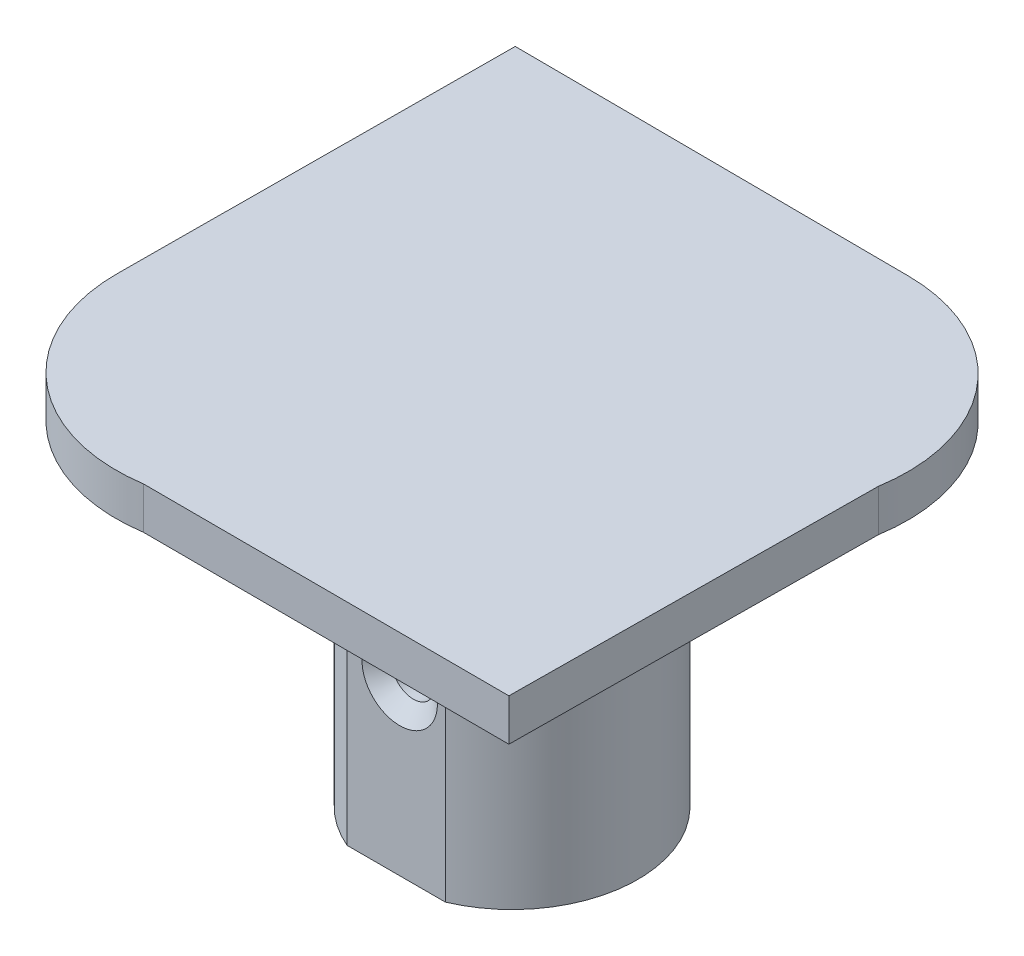
SolidWorks part; units mm, degrees
other "Camera1"
material "ABS"
ref_plane "Front Plane" through (0, 0, 0) normal (0, 0, 1) x (1, 0, 0)
ref_plane "Top Plane" through (0, 0, 0) normal (0, 1, 0) x (1, 0, 0)
ref_plane "Right Plane" through (0, 0, 0) normal (1, 0, 0) x (0, 0, -1)
sketch "Sketch2" plane through (0, 0, 0) normal (0, 1, 0) x (1, 0, 0)
  line L0 (2.8358, -0.2904) -> (10.2697, -0.2904)
  line L1 (2.8358, 17.2492) -> (10.2697, 17.2492)
  line L2 (6.5528, -0.2904) -> (6.5528, 17.2492) construction
  arc A0 (2.8358, 17.2492) -> (2.8358, -0.2904) centre (6.5528, 8.4794) ccw
  circle A1 centre (6.5528, 8.4794) radius 6.35
  arc A2 (10.2697, -0.2904) -> (10.2697, 17.2492) centre (6.5528, 8.4794) ccw
  dimension "D1" = 12.7
  dimension "D2" = 3.175
sketch "Sketch3" plane through (0, 0, 0) normal (0, 1, 0) x (1, 0, 0)
  line L0 (0, -12.8694) -> (27.7233, -12.933)
  line L1 (-14.7878, -0.0506) -> (-14.6178, 29.8917)
  line L4 (-14.6178, 29.8917) -> (27.7233, -12.933) construction
  line L5 (27.9746, 14.7893) -> (27.7233, -12.933)
  line L6 (15.3245, 29.7217) -> (-14.6178, 29.8917)
  arc A0 (-14.7878, -0.0506) -> (0, -12.8694) centre (-1.9188, -0.1438) ccw
  arc A2 (15.3245, 29.7217) -> (27.9746, 14.7893) centre (15.2716, 16.8524) cw
  point P8 (6.5528, 8.4794)
  dimension "D1" = 12.8694
extrude "Boss-Extrude1" add sketch "Sketch3" along normal blind 3.175 contours L4 L1 A0 L0 | L6 L4 L5 A2 | L0 L5 A2 L6 L1 A0 region at (-0.1371, 0, -1.8095) region at (13.2982, 0, -15.093)
ref_plane "Plane6" through (0, 0, 0) normal (0, -1, 0) x (-1, 0, 0)
sketch "Sketch11" plane through (0, 0, 0) normal (0, 1, 0) x (1, 0, 0)
  line L0 (20.07, -8.458) -> (21.4908, -8.4607)
  spline S0 degree 3 poles (22.9265, -1.3184) (22.9265, -4.6505) (22.9265, -7.9835) (22.9265, -11.3169) knots 3 3 3 3 4 4 4 4
  spline S1 degree 3 poles (12.9265, -1.3184) (16.2589, -1.3184) (19.5927, -1.3184) (22.9265, -1.3184) knots 2 2 2 2 3 3 3 3
  spline S2 degree 3 poles (12.9265, -11.3169) (12.9265, -7.9851) (12.9265, -4.6531) (12.9265, -1.3184) knots 1 1 1 1 2 2 2 2
  spline S3 degree 3 poles (22.9265, -11.3169) (19.5937, -11.3169) (16.2609, -11.3169) (12.9265, -11.3169) knots 0 0 0 0 1 1 1 1
  spline S4 degree 3 poles (15.7816, -4.1748) (17.1943, -4.1744) (20.0443, -4.1757) (20.0617, -4.1773) knots 0 0 0 0 1 1 1 1
  spline S5 degree 3 poles (20.0617, -4.1773) (20.0642, -4.1931) (20.0678, -7.048) (20.0673, -8.4607) knots 1 1 1 1 2 2 2 2
  spline S6 degree 2 poles (20.0673, -8.4607) (18.1734, -8.458) (17.2149, -8.458) knots 2 2 2 3 3 3
  spline S7 degree 3 poles (17.2149, -8.458) (17.2149, -8.9351) (17.2149, -9.4058) (17.2149, -9.8824) knots 3 3 3 3 4 4 4 4
  spline S8 degree 3 poles (17.2149, -9.8824) (16.7341, -9.8824) (16.2635, -9.8824) (15.7859, -9.8824) knots 4 4 4 4 5 5 5 5
  spline S9 degree 2 poles (15.7859, -9.8824) (15.7847, -9.8591) (15.7816, -4.1748) knots 5 5 5 6 6 6
  spline S10 degree 3 poles (15.7843, -4.1721) (15.3121, -4.1721) (14.8399, -4.1721) (14.3608, -4.1721) knots 0 0 0 0 1 1 1 1
  spline S11 degree 3 poles (14.3608, -4.1721) (14.3608, -3.6982) (14.3608, -3.2277) (14.3608, -2.7508) knots 1 1 1 1 2 2 2 2
  spline S12 degree 3 poles (14.3608, -2.7508) (14.8302, -2.7508) (15.3006, -2.7508) (15.7816, -2.7508) knots 2 2 2 2 3 3 3 3
  spline S13 degree 2 poles (15.7816, -2.7508) (15.7816, -3.2259) (15.7843, -4.1721) knots 3 3 3 4 4 4
  spline S15 degree 3 poles (20.07, -9.882) (20.07, -9.4069) (20.07, -8.9325) (20.07, -8.458) knots 2 2 2 2 3 3 3 3
  spline S16 degree 3 poles (21.4908, -9.882) (21.0214, -9.882) (20.551, -9.882) (20.07, -9.882) knots 1 1 1 1 2 2 2 2
  spline S17 degree 3 poles (21.4908, -8.4607) (21.4908, -8.9347) (21.4908, -9.4052) (21.4908, -9.882) knots 0 0 0 0 1 1 1 1
extrude "Boss-Extrude2" add sketch "Sketch2" against normal blind 25.4
sketch "Sketch14" plane through (0, 0, 0.2904) normal (0, 0, 1) x (1, 0, 0)
  line L0 (6.8149, -25.4) -> (6.8149, 0) construction
  line L1 (2.8358, -25.4) -> (10.2697, -25.4) construction
  line L2 (2.8358, 0) -> (10.2697, 0) construction
hole_wizard "CSK for #4 Flat Head Machine Screw (100)1" positions "Sketch15" profile "Sketch16" countersink size "#4" standard "ANSI Inch" end condition up to next
sketch "Sketch15" plane through (0, 0, 0.2904) normal (0, 0, 1) x (1, 0, 0)
  line L0 (6.8149, -25.4) -> (6.8149, 0) construction
  point P0 (6.8149, -12.7)
sketch "Sketch16" plane through (6.8149, -12.7, 0.2904) normal (1, 0, 0) x (0, -1, 0)
  line L0 (0, 0) -> (0, 2.4252)
  line L1 (0, 2.4252) -> (1.6319, 2.4252)
  line L2 (1.6319, 2.4252) -> (1.6319, 1.0284)
  line L3 (1.6319, 1.0284) -> (2.8575, 0)
  line L5 (2.8575, 0) -> (0, 0)
  line L6 (-1.6319, 1.0284) -> (-2.8575, 0) construction
  line L11 (0, -6.35) -> (0, 107.95) construction
  dimension "Thru Hole Dia." = 3.2639
  dimension "Thru Hole Depth" = 2.4252
  dimension "Near C'Sink Dia." = 5.715
  dimension "Near C'Sink Angle" = 100
fillet "Fillet1" radius 5 2 edges at (-2.9722, 0, -8.4794) (16.0778, 0, -8.4794)
